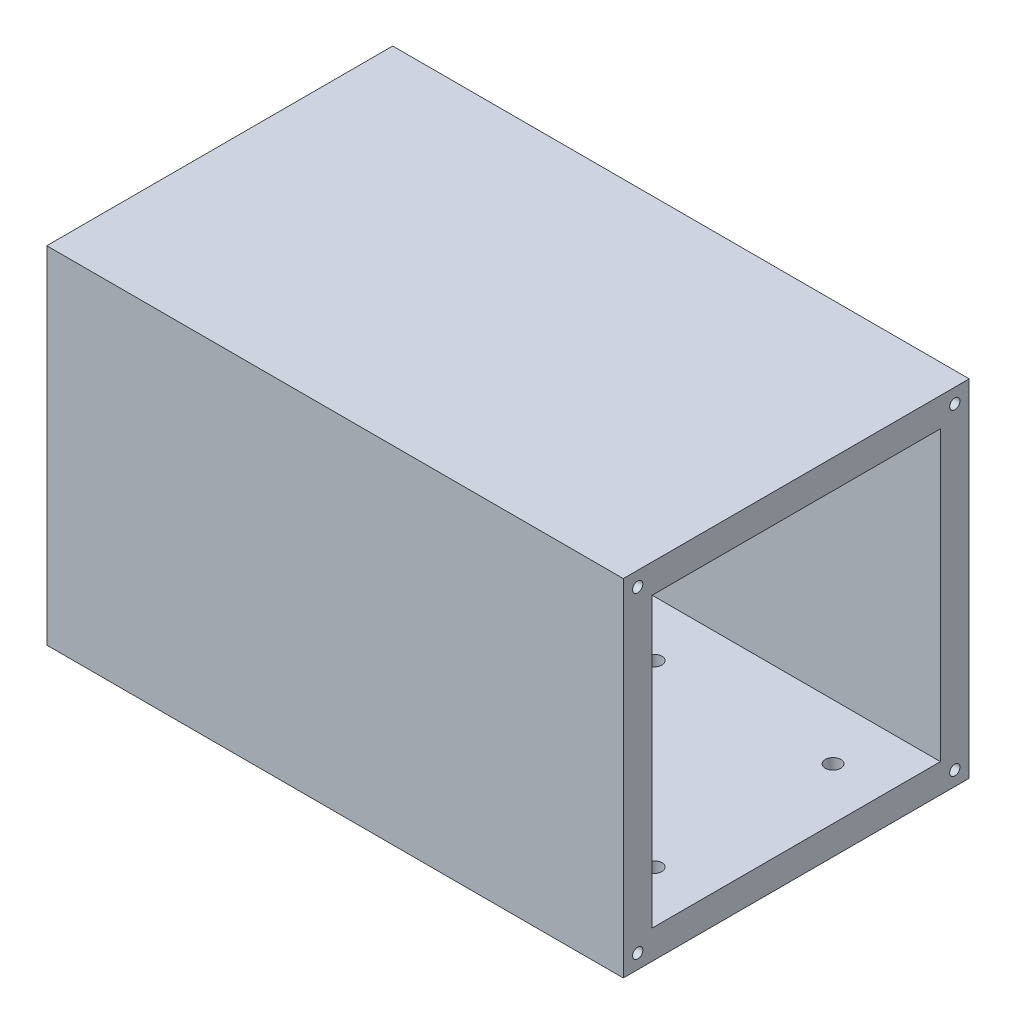
SolidWorks part; units mm, degrees
ref_plane "Front Plane" through (0, 0, 0) normal (0, 0, 1) x (1, 0, 0)
ref_plane "Top Plane" through (0, 0, 0) normal (0, 1, 0) x (1, 0, 0)
ref_plane "Right Plane" through (0, 0, 0) normal (1, 0, 0) x (0, 0, -1)
sketch "Sketch1" plane through (0, 0, 0) normal (1, 0, 0) x (0, 0, -1)
  line L1 (-38.1, 38.1) -> (38.1, 38.1)
  line L2 (-38.1, 38.1) -> (-38.1, -38.1)
  line L3 (-38.1, -38.1) -> (38.1, -38.1)
  line L4 (38.1, 38.1) -> (38.1, -38.1)
  line L5 (-38.1, 38.1) -> (38.1, -38.1) construction
  line L6 (-38.1, -38.1) -> (38.1, 38.1) construction
  line L7 (-31.75, -31.75) -> (31.75, -31.75)
  line L8 (-31.75, -31.75) -> (-31.75, 31.75)
  line L9 (-31.75, 31.75) -> (31.75, 31.75)
  line L10 (31.75, -31.75) -> (31.75, 31.75)
  line L11 (-31.75, -31.75) -> (31.75, 31.75) construction
  line L12 (-31.75, 31.75) -> (31.75, -31.75) construction
  point P0 (0, 0)
  point P6 (0, 0)
  dimension "D1" = 76.2
  dimension "D2" = 76.2
  dimension "D3" = 6.35
  dimension "D4" = 6.35
extrude "Boss-Extrude1" add sketch "Sketch1" along normal blind 63.5 and the other way blind 63.5
hole_wizard "#4-40 Tapped Hole1" positions "Sketch2" profile "Sketch3" tap size "#4-40" standard "ANSI Inch"
sketch "Sketch2" plane through (63.5, 0, 0) normal (1, 0, 0) x (0, 0, -1)
  line L0 (-38.1, 38.1) -> (-38.1, -38.1) construction
  line L1 (38.1, 38.1) -> (-38.1, 38.1) construction
  line L2 (38.1, -38.1) -> (38.1, 38.1) construction
  line L3 (-38.1, -38.1) -> (38.1, -38.1) construction
  point P0 (-34.925, 34.925)
  point P2 (34.925, 34.925)
  point P4 (34.925, -34.925)
  point P6 (-34.925, -34.925)
  dimension "D1" = 3.175
  dimension "D2" = 3.175
  dimension "D3" = 3.175
  dimension "D4" = 3.175
  dimension "D5" = 3.175
  dimension "D6" = 3.175
  dimension "D7" = 3.175
  dimension "D8" = 3.175
sketch "Sketch3" plane through (63.5, 34.925, 34.925) normal (0, 1, 0) x (0, 0, -1)
  line L0 (0, 0) -> (0, 8.2992)
  line L1 (0, 8.2992) -> (1.1303, 7.62)
  line L2 (1.1303, 7.62) -> (1.1303, 0)
  line L5 (1.1303, 0) -> (0, 0)
  line L10 (0, 8.2992) -> (-1.1303, 7.62) construction
  line L11 (0, -6.35) -> (0, 107.95) construction
  dimension "Tap Drill Dia." = 2.2606
  dimension "Tap Drill Depth" = 7.62
  dimension "Drill Angle" = 118
cosmetic thread "Hole Thread1" parameters "D1"=5.588, "D2"=2.8448
cosmetic thread "Hole Thread2" parameters "D1"=5.588, "D2"=2.8448
cosmetic thread "Hole Thread3" parameters "D1"=5.588, "D2"=2.8448
cosmetic thread "Hole Thread4" parameters "D1"=5.588, "D2"=2.8448
mirror "Mirror1" about plane through (0, 0, 0) normal (1, 0, 0) of "#4-40 Tapped Hole1"
hole_wizard "CBORE for M3 SHCS1" positions "Sketch4" profile "Sketch5" counterbore size "M3" standard "ANSI Metric" end condition up to next
sketch "Sketch4" plane through (0, -38.1, 0) normal (0, -1, 0) x (-1, 0, 0)
  line L0 (63.5, -38.1) -> (-63.5, -38.1) construction
  line L1 (63.5, 38.1) -> (-63.5, 38.1) construction
  line L3 (-63.5, -38.1) -> (-63.5, 38.1) construction
  point P0 (-52.1, 19.5)
  point P2 (-12.7, 19.5)
  point P4 (-12.7, -19.9)
  point P6 (-52.1, -19.9)
  dimension "D1" = 39.4
  dimension "D2" = 39.4
  dimension "D3" = 39.4
  dimension "D4" = 18.2
  dimension "D5" = 18.6
  dimension "D6" = 50.8
sketch "Sketch5" plane through (52.1, -38.1, -19.5) normal (1, 0, 0) x (0, 0, -1)
  line L0 (0, 0) -> (0, 6.35)
  line L1 (0, 6.35) -> (1.7, 6.35)
  line L3 (1.7, 6.35) -> (1.7, 3)
  line L4 (1.7, 3) -> (3.25, 3)
  line L5 (3.25, 3) -> (3.25, 0)
  line L7 (3.25, 0) -> (0, 0)
  line L11 (0, -6.35) -> (0, 107.95) construction
  dimension "Thru Hole Dia." = 3.4
  dimension "Thru Hole Depth" = 6.35
  dimension "C'Bore Dia." = 6.5
  dimension "C'Bore Depth" = 3
